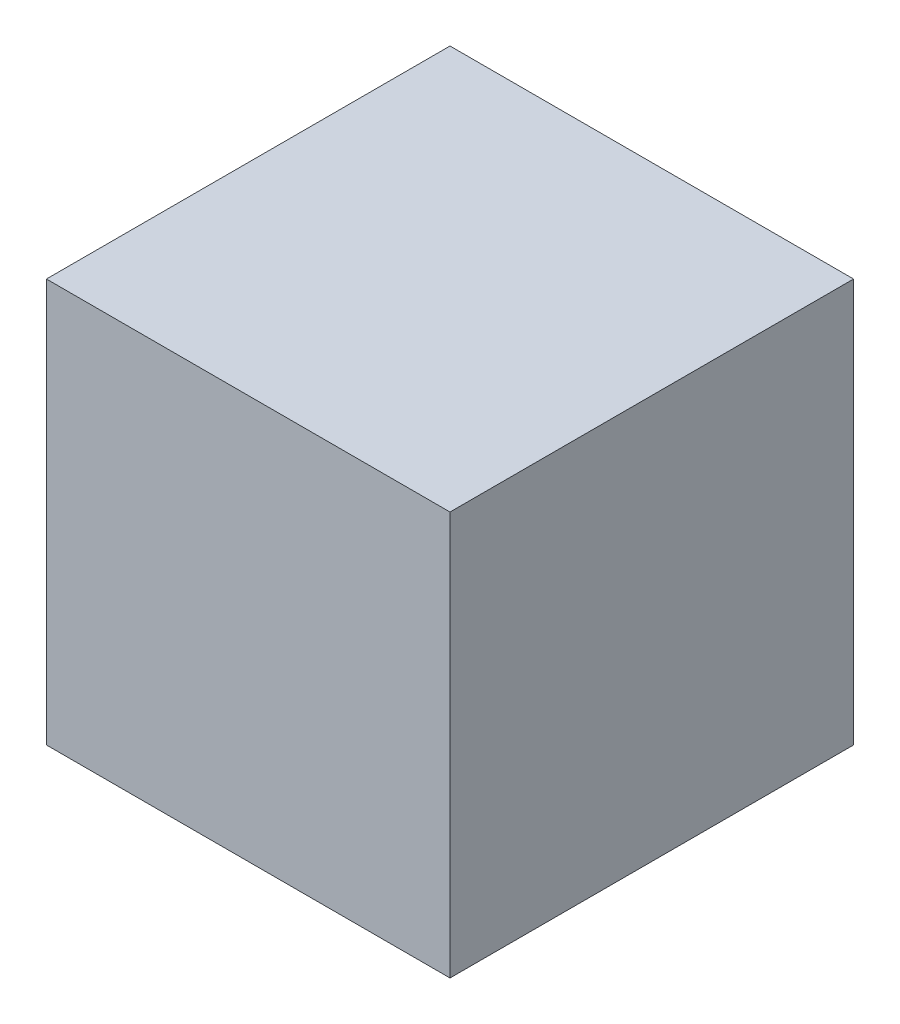
SolidWorks part; units mm, degrees
material "Plastiche personalizzate"
ref_plane "Piano frontale" through (0, 0, 0) normal (0, 0, 1) x (1, 0, 0)
ref_plane "Piano superiore" through (0, 0, 0) normal (0, 1, 0) x (1, 0, 0)
ref_plane "Piano destro" through (0, 0, 0) normal (1, 0, 0) x (0, 0, -1)
sketch "Schizzo1" plane through (0, 0, 0) normal (0, 0, 1) x (1, 0, 0)
  line L1 (47.08, -47.08) -> (-47.08, -47.08)
  line L2 (47.08, -47.08) -> (47.08, 47.08)
  line L3 (47.08, 47.08) -> (-47.08, 47.08)
  line L4 (-47.08, -47.08) -> (-47.08, 47.08)
  line L5 (47.08, -47.08) -> (-47.08, 47.08) construction
  line L6 (47.08, 47.08) -> (-47.08, -47.08) construction
  point P0 (0, 0)
  dimension "D1" = 94.16
extrude "Estrusione-Estrusione1" add sketch "Schizzo1" along normal blind 94.16
ref_plane "Piano1" through (0, 0, 0) normal (1, 0, 0) x (0, 0, -1)
ref_plane "Piano2" through (0, 0, 47.08) normal (0, 0, 1) x (1, 0, 0)
sketch "Sketch1" plane through (0, 47.08, 0) normal (0, 1, 0) x (1, 0, 0)
  line L0 (-47.08, 0) -> (0, -47.08)
  line L1 (0, -47.08) -> (47.08, 0)
  line L2 (0, -47.08) -> (0, -94.16)
  line L3 (47.08, -94.16) -> (-47.08, -94.16) construction
  circle A0 centre (0, -47.08) radius 66.5812
